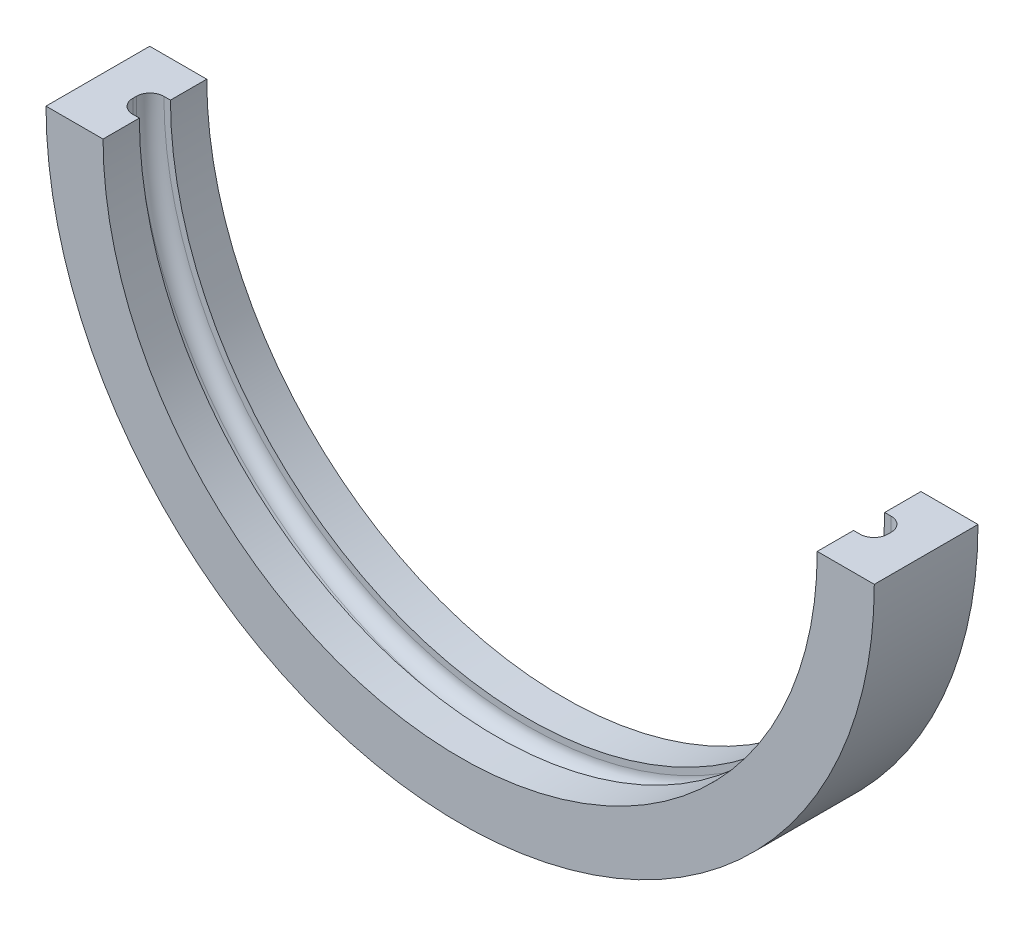
SolidWorks part; units mm, degrees
ref_plane "Front Plane" through (0, 0, 0) normal (0, 0, 1) x (1, 0, 0)
ref_plane "Top Plane" through (0, 0, 0) normal (0, 1, 0) x (1, 0, 0)
ref_plane "Right Plane" through (0, 0, 0) normal (1, 0, 0) x (0, 0, -1)
sketch "Sketch1" plane through (0, 0, 0) normal (0, 0, 1) x (1, 0, 0)
  line L0 (-69.342, 76.073) -> (-76.073, 76.073)
  line L1 (69.342, 76.073) -> (76.073, 76.073)
  circle A0 centre (0, 76.073) radius 76.073
  circle A1 centre (0, 76.073) radius 69.342
  dimension "D1" = 152.146
  dimension "D2" = 138.684
extrude "Boss-Extrude1" add sketch "Sketch1" along normal blind 5.715 contours A1 L0 A0 L1 region at (0, 5.03, 0)
sketch "Sketch3" plane through (0, 0, 5.715) normal (0, 0, 1) x (1, 0, 0)
  line L0 (-65.5955, 76.073) -> (-76.073, 76.073)
  line L1 (65.5955, 76.073) -> (76.073, 76.073)
  circle A0 centre (0, 76.073) radius 76.073
  circle A1 centre (0, 76.073) radius 65.5955
  arc M3 (69.342, 76.073) -> (-69.342, 76.073) centre (0, 76.073) cw
  line M4 (-69.342, 76.073) -> (-76.073, 76.073)
  arc M5 (-76.073, 76.073) -> (76.073, 76.073) centre (0, 76.073) ccw
  line M6 (76.073, 76.073) -> (69.342, 76.073)
  dimension "D1" = 131.191
extrude "Boss-Extrude2" add sketch "Sketch3" along normal blind 6.6675 contours A1 L0 L1 M3 | M6 M3 M4 M5 region at (0, 8.927, 5.715) region at (0, 5.03, 5.715)
sketch "Sketch4" plane through (0, 0, 0) normal (0, 0, -1) x (-1, 0, 0)
  line L0 (-65.5955, 76.073) -> (-76.073, 76.073)
  line L1 (65.5955, 76.073) -> (76.073, 76.073)
  circle A0 centre (0, 76.073) radius 76.073
  circle A1 centre (0, 76.073) radius 65.5955
  arc M3 (69.342, 76.073) -> (-69.342, 76.073) centre (0, 76.073) cw
  line M4 (-69.342, 76.073) -> (-76.073, 76.073)
  arc M5 (-76.073, 76.073) -> (76.073, 76.073) centre (0, 76.073) ccw
  line M6 (76.073, 76.073) -> (69.342, 76.073)
extrude "Boss-Extrude3" add sketch "Sketch4" along normal blind 6.6675 contours A1 L0 L1 M3 | M6 M3 M4 M5 region at (0, 8.927, 0) region at (0, 5.03, 0)
fillet "Fillet1" radius 2.54 2 edges at (0, 6.731, 5.715) (0, 6.731, 0)
sketch "Sketch5" plane through (0, 0, 0) normal (0, 1, 0) x (1, 0, 0)
  line L0 (64.2819, -2.8575) -> (-64.2819, -2.8575) construction
  circle A0 centre (0, -2.8575) radius 1.524
  dimension "D1" = 3.048
extrude "Cut-Extrude1" cut sketch "Sketch5" along normal blind 6.35
sketch "Sketch6" plane through (0, 0, 12.3825) normal (0, 0, 1) x (1, 0, 0)
  line L1 (69.7959, 76.073) -> (75.8284, 76.073)
  line L2 (69.7959, 76.073) -> (69.7959, 69.977)
  line L3 (69.7959, 69.977) -> (75.8284, 69.977)
  line L4 (75.8284, 76.073) -> (75.8284, 69.977)
  line L5 (0, 0) -> (0, 90.126) construction
  line L6 (-75.8284, 69.977) -> (-82.0776, 69.977)
  line L7 (75.8284, 76.073) -> (82.0776, 76.073)
  line L8 (75.8284, 76.073) -> (75.8284, 69.977)
  line L9 (75.8284, 69.977) -> (82.0776, 69.977)
  line L10 (82.0776, 76.073) -> (82.0776, 69.977)
  line L11 (-82.0776, 76.073) -> (-82.0776, 69.977)
  line L12 (-75.8284, 76.073) -> (-82.0776, 76.073)
  line L13 (-75.8284, 76.073) -> (-75.8284, 69.977)
  line L14 (-69.7959, 69.977) -> (-75.8284, 69.977)
  line L15 (-75.8284, 76.073) -> (-75.8284, 69.977)
  line L16 (-69.7959, 76.073) -> (-75.8284, 76.073)
  line L17 (-69.7959, 76.073) -> (-69.7959, 69.977)
  arc A1 (-76.073, 76.073) -> (76.073, 76.073) centre (0, 76.073) ccw construction
  line M11 (-65.5955, 76.073) -> (-76.073, 76.073)
  arc M12 (-76.073, 76.073) -> (76.073, 76.073) centre (0, 76.073) ccw
  line M13 (76.073, 76.073) -> (65.5955, 76.073)
  dimension "D1" = 6.096
  dimension "D2" = 6.0325
extrude "Cut-Extrude2" [suppressed] cut sketch "Sketch6" against normal through all contours L12 L11 L6 M12 | L17 L13 L14 M11 | L10 L7 L9 M12 | L4 L2 L3 M13
sketch "Sketch7" [suppressed] plane through (0, 0, 12.3825) normal (0, 0, 1) x (1, 0, 0)
  line L0 (-69.7959, 69.977) -> (-75.8284, 69.977) construction
  line L1 (-72.8121, 69.977) -> (-85.9884, 69.977)
  line L2 (-72.8121, 69.977) -> (-72.8121, 79.2871)
  line L3 (-72.8121, 79.2871) -> (-85.9884, 79.2871)
  line L4 (-85.9884, 69.977) -> (-85.9884, 79.2871)
  line L5 (0, 20.0433) -> (0, 96.673) construction
  line L6 (72.8121, 79.2871) -> (85.9884, 79.2871)
  line L7 (85.9884, 69.977) -> (85.9884, 79.2871)
  line L8 (72.8121, 69.977) -> (85.9884, 69.977)
  line L9 (72.8121, 69.977) -> (72.8121, 79.2871)
extrude "Cut-Extrude3" [suppressed] cut sketch "Sketch7" against normal through all contours L2 L1 L4 L3 | L6 L7 L8 L9
